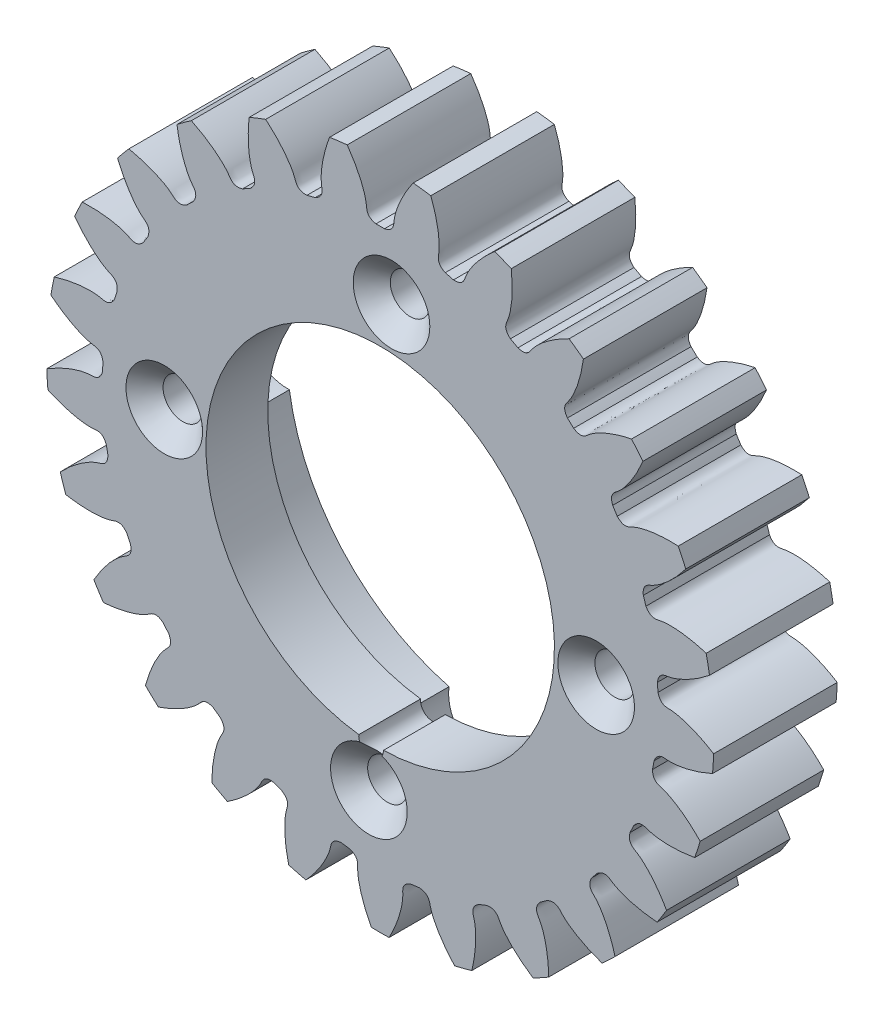
SolidWorks part; units mm, degrees
ref_plane "前视基准面" through (0, 0, 0) normal (0, 0, 1) x (1, 0, 0)
ref_plane "上视基准面" through (0, 0, 0) normal (0, 1, 0) x (1, 0, 0)
ref_plane "右视基准面" through (0, 0, 0) normal (1, 0, 0) x (0, 0, -1)
sketch "草图1" plane through (0, 0, 0) normal (0, 0, 1) x (1, 0, 0)
  circle A0 centre (0, 0) radius 27
extrude "凸台-拉伸1" add sketch "草图1" along normal blind 10
ref_axis "基准轴1" through (0, 0, 10) along (0, 0, -1)
sketch "草图2" plane through (0, 0, 0) normal (0, 0, 1) x (1, 0, 0)
  line L0 (0, 0) -> (0, 27) construction
  circle A0 centre (0, 0) radius 27 construction
  arc A1 (0.3441, 22.4974) -> (-0.3441, 22.4974) centre (0, 0) ccw
  arc A2 (6.4105, 30.6297) -> (-6.4105, 30.6297) centre (0, 0) ccw
  spline S0 degree 3 poles (0.3441, 22.4974) (1.1467, 22.6702) (1.071, 23.1545) (1.1484, 23.6361) (1.1592, 23.6962) (1.1732, 23.7653) (1.1905, 23.8433) (1.2116, 23.93) (1.2368, 24.0254) (1.2665, 24.1293) (1.301, 24.2416) (1.3407, 24.3621) (1.3859, 24.4906) (1.437, 24.6271) (1.4943, 24.7712) (1.5581, 24.9227) (1.6287, 25.0816) (1.7064, 25.2475) (1.7916, 25.4203) (1.8846, 25.5997) (1.9857, 25.7854) (2.095, 25.9773) (2.2131, 26.175) (2.34, 26.3782) (2.4761, 26.5868) (2.6216, 26.8004) (2.7768, 27.0186) (2.9419, 27.2413) (3.1172, 27.468) (3.303, 27.6986) (3.4993, 27.9325) (3.7064, 28.1696) (3.9246, 28.4094) (4.1539, 28.6517) (4.3947, 28.896) (4.647, 29.142) (4.9111, 29.3893) (5.187, 29.6376) (5.475, 29.8865) (5.8799, 30.2225) (6.1949, 30.4682) (6.4105, 30.6297) knots 0 0 0 0 0.130741 0.135745 0.141658 0.148481 0.156214 0.164857 0.174409 0.184871 0.196243 0.208524 0.221715 0.235816 0.250827 0.266748 0.283578 0.301318 0.319968 0.339527 0.359996 0.381375 0.403664 0.426862 0.450971 0.475988 0.501916 0.528753 0.556501 0.585157 0.614724 0.6452 0.676587 0.708882 0.742088 0.776203 0.811228 0.847163 0.884008 0.921762 1 1 1 1
  spline S1 degree 3 poles (-0.3441, 22.4974) (-1.1467, 22.6702) (-1.071, 23.1545) (-1.1484, 23.6361) (-1.1592, 23.6962) (-1.1732, 23.7653) (-1.1905, 23.8433) (-1.2116, 23.93) (-1.2368, 24.0254) (-1.2665, 24.1293) (-1.301, 24.2416) (-1.3407, 24.3621) (-1.3859, 24.4906) (-1.437, 24.6271) (-1.4943, 24.7712) (-1.5581, 24.9227) (-1.6287, 25.0816) (-1.7064, 25.2475) (-1.7916, 25.4203) (-1.8846, 25.5997) (-1.9857, 25.7854) (-2.095, 25.9773) (-2.2131, 26.175) (-2.34, 26.3782) (-2.4761, 26.5868) (-2.6216, 26.8004) (-2.7768, 27.0186) (-2.9419, 27.2413) (-3.1172, 27.468) (-3.303, 27.6986) (-3.4993, 27.9325) (-3.7064, 28.1696) (-3.9246, 28.4094) (-4.1539, 28.6517) (-4.3947, 28.896) (-4.647, 29.142) (-4.9111, 29.3893) (-5.187, 29.6376) (-5.475, 29.8865) (-5.8799, 30.2225) (-6.1949, 30.4682) (-6.4105, 30.6297) knots 0 0 0 0 0.130741 0.135745 0.141658 0.148481 0.156214 0.164857 0.174409 0.184871 0.196243 0.208524 0.221715 0.235816 0.250827 0.266748 0.283578 0.301318 0.319968 0.339527 0.359996 0.381375 0.403664 0.426862 0.450971 0.475988 0.501916 0.528753 0.556501 0.585157 0.614724 0.6452 0.676587 0.708882 0.742088 0.776203 0.811228 0.847163 0.884008 0.921762 1 1 1 1
extrude "切除-拉伸1" cut sketch "草图2" along normal through all
pattern_circular "阵列(圆周)1" count 25 every 14.4 about axis through (0, 0, 10) along (0, 0, -1) of "切除-拉伸1"
sketch "草图3" plane through (0, 0, 0) normal (0, 0, 1) x (1, 0, 0)
  circle A0 centre (0, 0) radius 25 construction
  dimension "Dn" = 50
sketch "草图4" plane through (0, 0, 10) normal (0, 0, 1) x (1, 0, 0)
  line L0 (-0.9159, -17.476) -> (-0.7379, -14.0807) construction
  line L1 (0, 0) -> (0, -17.5) construction
  circle A0 centre (0, 0) radius 17.5 construction
  circle A1 centre (-0.9159, -17.476) radius 1.6
  arc A10 (0.2619, -14.0976) -> (-1.7341, -13.993) centre (0, 0) ccw
  arc A11 (-1.7341, -13.993) -> (0.2619, -14.0976) centre (-0.7379, -14.0807) ccw
  circle A12 centre (-17.476, 0.9159) radius 1.6
  circle A13 centre (0.9159, 17.476) radius 1.6
  circle A14 centre (17.476, -0.9159) radius 1.6
  point P18 (0, 0)
  dimension "D1" = 35
  dimension "D2" = 3.2
  dimension "D3" = 28.2
  dimension "D4" = 2
  dimension "D5" = 3
  dimension "D6" = 4
extrude "切除-拉伸2" cut sketch "草图4" against normal through all
sketch "草图5" plane through (0, 0, 0) normal (0, 0, -1) x (-1, 0, 0)
  arc A0 (-2.6319, -17.3515) -> (4.4312, -16.9814) centre (0.9159, -17.476) ccw
  arc A1 (17.3515, -2.6319) -> (16.9814, 4.4312) centre (17.476, 0.9159) ccw
  arc A2 (2.6319, 17.3515) -> (-4.4312, 16.9814) centre (-0.9159, 17.476) ccw
  arc A3 (-17.3515, 2.6319) -> (-16.9814, -4.4312) centre (-17.476, -0.9159) ccw
  arc A4 (16.9814, 4.4312) -> (2.6319, 17.3515) centre (0, 0) ccw
  arc A5 (4.4312, -16.9814) -> (17.3515, -2.6319) centre (0, 0) ccw
  arc A6 (-16.9814, -4.4312) -> (-2.6319, -17.3515) centre (0, 0) ccw
  arc A7 (-4.4312, 16.9814) -> (-17.3515, 2.6319) centre (0, 0) ccw
  circle A8 centre (17.476, 0.9159) radius 1.6 construction
  circle A11 centre (-0.9159, 17.476) radius 1.6 construction
  circle A12 centre (-17.476, -0.9159) radius 1.6 construction
  dimension "D1" = 7.1
  dimension "D2" = 17.55
extrude "切除-拉伸4" cut sketch "草图5" against normal blind 5
chamfer "倒角1" distance 1.5 angle 45 4 edges at (0.6841, -17.476, 10) (-15.876, 0.9159, 10) (2.5159, 17.476, 10) (19.076, -0.9159, 10)
